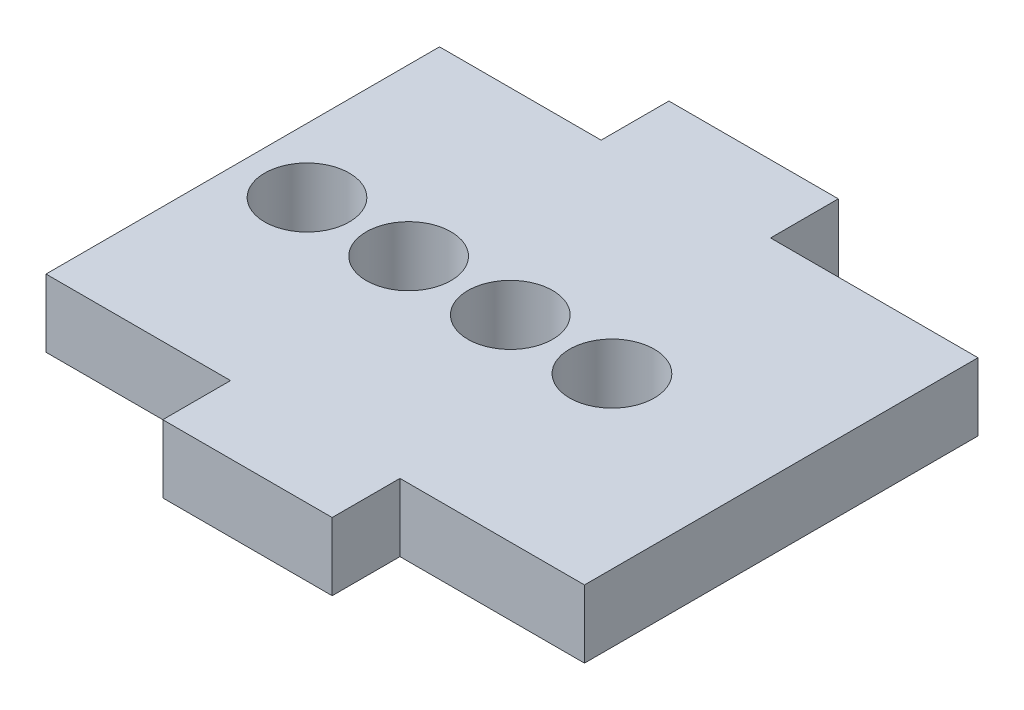
SolidWorks part; units mm, degrees
ref_plane "Front Plane" through (0, 0, 0) normal (0, 0, 1) x (1, 0, 0)
ref_plane "Top Plane" through (0, 0, 0) normal (0, 1, 0) x (1, 0, 0)
ref_plane "Right Plane" through (0, 0, 0) normal (1, 0, 0) x (0, 0, -1)
sketch "Sketch1" plane through (0, 0, 0) normal (0, 1, 0) x (1, 0, 0)
  line L0 (36.7869, 11.6138) -> (44.4925, 11.6138)
  line L1 (27.5186, 11.6138) -> (12.7082, 11.6138)
  line L2 (27.5186, -11.6138) -> (12.7082, -11.6138)
  line L3 (0, 0) -> (46.96, 0) construction
  line L4 (36.7869, -11.6138) -> (44.4925, -11.6138)
  line L5 (44.4925, 11.6138) -> (44.4925, -11.6138)
  line L10 (27.5186, 11.6138) -> (36.7869, 11.6138)
  line L11 (12.7082, 11.6138) -> (12.7082, -11.6138)
  line L15 (27.5186, -11.6138) -> (36.7869, -11.6138)
  circle A15 centre (16.5, 0) radius 2.5
  circle A16 centre (22.5, 0) radius 2.5
  circle A17 centre (28.5, 0) radius 2.5
  circle A18 centre (34.5, 0) radius 2.5
extrude "Boss-Extrude2" add sketch "Sketch1" along normal blind 4
sketch "Sketch12" plane through (0, 0, -11.6138) normal (0, 0, -1) x (-1, 0, 0)
  line L3 (-44.4925, 4) -> (-12.7082, 4) construction
  line L4 (-32.2475, 0) -> (-22.2475, 0)
  line L5 (-32.2475, 0) -> (-32.2475, 4)
  line L6 (-32.2475, 4) -> (-22.2475, 4)
  line L7 (-22.2475, 0) -> (-22.2475, 4)
  point P6 (-27.2475, 2)
  dimension "D1" = 10
extrude "Boss-Extrude4" add sketch "Sketch12" along normal blind 4
sketch "Sketch13" plane through (0, 4, 0) normal (0, 1, 0) x (1, 0, 0)
  line L0 (16.5, 0) -> (34.5, 0) construction
sketch "Sketch14" plane through (0, 0, 11.6138) normal (0, 0, 1) x (1, 0, 0)
  line L0 (12.7082, 2) -> (44.4925, 2) construction
  line L1 (12.7082, 4) -> (12.7082, 0) construction
  line L2 (44.4925, 4) -> (44.4925, 0) construction
  line L3 (12.7082, 4) -> (44.4925, 4) construction
  line L4 (23.6003, 0) -> (33.6003, 0)
  line L5 (23.6003, 0) -> (23.6003, 4)
  line L6 (23.6003, 4) -> (33.6003, 4)
  line L7 (33.6003, 0) -> (33.6003, 4)
  line L8 (23.6003, 0) -> (33.6003, 4) construction
  line L9 (23.6003, 4) -> (33.6003, 0) construction
  point P6 (28.6003, 2)
  dimension "D1" = 10
extrude "Boss-Extrude5" add sketch "Sketch14" along normal blind 4
sketch "Sketch5" plane through (0, 0, 0) normal (0, -1, 0) x (1, 0, 0)
  line L0 (16.5, 0) -> (34.5, 0)
  circle A3 centre (16.5, 0) radius 2.5
  circle A4 centre (22.5, 0) radius 2.5
  circle A5 centre (28.5, 0) radius 2.5
  circle A6 centre (34.5, 0) radius 2.5
  dimension "D2" = 4
